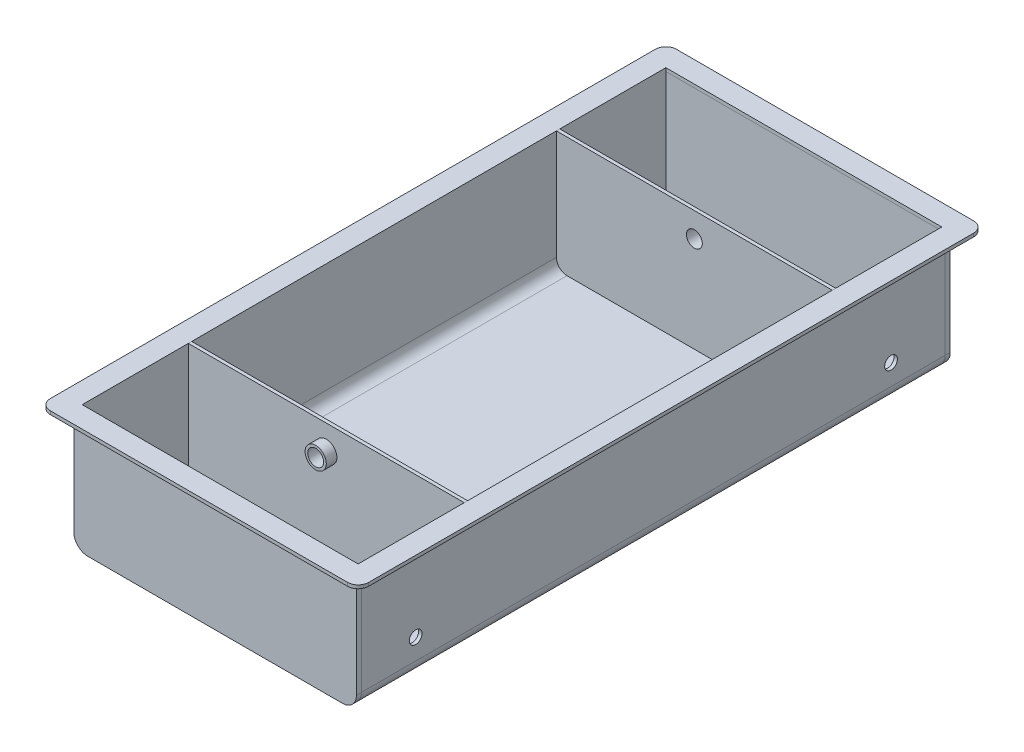
SolidWorks part; units mm, degrees
material "5052-H32"
ref_plane "Front Plane" through (0, 0, 0) normal (0, 0, 1) x (1, 0, 0)
ref_plane "Top Plane" through (0, 0, 0) normal (0, 1, 0) x (1, 0, 0)
ref_plane "Right Plane" through (0, 0, 0) normal (1, 0, 0) x (0, 0, -1)
sketch "Sketch2" plane through (0, 0, 0) normal (0, 0, 1) x (1, 0, 0)
  line L0 (-130, 0) -> (130, 0)
  line L1 (-130, 0) -> (-130, 110)
  line L2 (130, 0) -> (130, 110)
  line L3 (-133.175, -3.175) -> (-133.175, 110)
  line L4 (-133.175, -3.175) -> (133.175, -3.175)
  line L5 (133.175, -3.175) -> (133.175, 110)
  line L6 (-133.175, 110) -> (-130, 110)
  line L7 (130, 110) -> (133.175, 110)
  point P4 (0, 0)
  dimension "D1" = 260
  dimension "D3" = 110
  dimension "D4" = 110
  dimension "D2" = 3.175
  dimension "D5" = 3.175
  dimension "D6" = 3.175
extrude "Interior Dim" add sketch "Sketch2" against normal blind 550
fillet "Fillet2" radius 10 2 edges at (-130, 0, -275) (130, 0, -275)
fillet "Fillet3" radius 13.175 2 edges at (-133.175, -3.175, -275) (133.175, -3.175, -275)
ref_plane "Plane1" through (0, 0, 0) normal (0, 0, 1) x (1, 0, 0)
sketch "Sketch4" plane through (0, 0, 0) normal (0, 0, 1) x (1, 0, 0)
  line L0 (-130, 110) -> (130, 110)
  line L9 (-120, -3.175) -> (120, -3.175)
  line L10 (133.175, 10) -> (133.175, 110)
  line L11 (133.175, 110) -> (130, 110)
  line L12 (130, 110) -> (130, 10)
  line L13 (120, 0) -> (-120, 0)
  line L14 (-130, 10) -> (-130, 110)
  line L15 (-130, 110) -> (-133.175, 110)
  line L16 (-133.175, 110) -> (-133.175, 10)
  line L17 (-120, -3.175) -> (120, -3.175)
  line L18 (133.175, 10) -> (133.175, 110)
  line L19 (133.175, 110) -> (130, 110)
  line L23 (-130, 110) -> (-133.175, 110)
  line L24 (-133.175, 110) -> (-133.175, 10)
  arc A4 (120, -3.175) -> (133.175, 10) centre (120, 10) ccw
  arc A5 (120, 0) -> (130, 10) centre (120, 10) ccw
  arc A6 (-130, 10) -> (-120, 0) centre (-120, 10) ccw
  arc A7 (120, -3.175) -> (133.175, 10) centre (120, 10) ccw
  arc A9 (-133.175, 10) -> (-120, -3.175) centre (-120, 10) ccw
  arc A10 (-133.175, 10) -> (-120, -3.175) centre (-120, 10) ccw
  dimension "D1" = 0
extrude "Endcap1" add sketch "Sketch4" along normal blind 4.7625 separate body
ref_plane "Plane2" through (0, 0, -550) normal (0, 0, -1) x (-1, 0, 0)
sketch "Sketch5" plane through (0, 0, -550) normal (0, 0, -1) x (-1, 0, 0)
  line L8 (133.175, 110) -> (-133.175, 110)
  line L16 (-133.175, 110) -> (-133.175, 10)
  line L17 (-120, -3.175) -> (120, -3.175)
  line L18 (133.175, 10) -> (133.175, 110)
  line L19 (133.175, 110) -> (130, 110)
  line L20 (130, 110) -> (130, 10)
  line L21 (120, 0) -> (-120, 0)
  line L22 (-130, 10) -> (-130, 110)
  line L23 (-130, 110) -> (-133.175, 110)
  line L24 (-133.175, 110) -> (-133.175, 10)
  line L25 (-120, -3.175) -> (120, -3.175)
  line L26 (133.175, 10) -> (133.175, 110)
  arc A6 (-133.175, 10) -> (-120, -3.175) centre (-120, 10) ccw
  arc A7 (-133.175, 10) -> (-120, -3.175) centre (-120, 10) ccw
  arc A8 (120, 0) -> (130, 10) centre (120, 10) ccw
  arc A9 (-130, 10) -> (-120, 0) centre (-120, 10) ccw
  arc A12 (120, -3.175) -> (133.175, 10) centre (120, 10) ccw
  arc A13 (120, -3.175) -> (133.175, 10) centre (120, 10) ccw
  dimension "D1" = 0
ref_plane "Compartment1" through (0, 0, -100) normal (0, 0, -1) x (-1, 0, 0)
sketch "Sketch7" plane through (0, 0, -100) normal (0, 0, -1) x (-1, 0, 0)
  line L1 (130, 110) -> (-130, 110)
  line L10 (-120, -3.175) -> (120, -3.175)
  line L11 (-133.175, 110) -> (-133.175, 10)
  line L12 (-130, 110) -> (-133.175, 110)
  line L13 (-130, 10) -> (-130, 110)
  line L14 (120, 0) -> (-120, 0)
  line L15 (130, 110) -> (130, 10)
  line L16 (133.175, 110) -> (130, 110)
  line L17 (133.175, 10) -> (133.175, 110)
  line L21 (-130, 10) -> (-130, 110)
  line L22 (120, 0) -> (-120, 0)
  line L23 (130, 110) -> (130, 10)
  arc A5 (-130, 10) -> (-120, 0) centre (-120, 10) ccw
  arc A6 (120, 0) -> (130, 10) centre (120, 10) ccw
  arc A7 (-133.175, 10) -> (-120, -3.175) centre (-120, 10) ccw
  arc A8 (120, -3.175) -> (133.175, 10) centre (120, 10) ccw
  arc A9 (-130, 10) -> (-120, 0) centre (-120, 10) ccw
  arc A10 (120, 0) -> (130, 10) centre (120, 10) ccw
  dimension "D1" = 0
extrude "Compartment1_Boss" add sketch "Sketch7" along normal blind 3.175 separate body contours L22 A10 L23 L1 L21 A9 region at (0, 55.0793, -100)
ref_plane "Plane5" through (0, 110, 0) normal (0, 1, 0) x (1, 0, 0)
sketch "Sketch9" plane through (0, 110, 0) normal (0, 1, 0) x (1, 0, 0)
  line L0 (62.2463, 550) -> (-62.2463, 550) construction
  line L1 (-130, 550) -> (130, 550)
  line L2 (-130, 550) -> (-130, 0)
  line L3 (-130, 0) -> (130, 0)
  line L4 (130, 550) -> (130, 0)
  line L5 (-130, 0) -> (-130, 550) construction
  line L6 (-62.2463, 0) -> (62.2463, 0) construction
  line L7 (130, 550) -> (130, 0) construction
  line L8 (-150, 570) -> (-150, -20)
  line L9 (-150, -20) -> (150, -20)
  line L10 (150, 570) -> (150, -20)
  line L11 (-150, 570) -> (150, 570)
extrude "Lid_Flange" add sketch "Sketch9" along normal blind 3.175 separate body contours L11 L8 L9 L10 L1 L4 region at (0, 110, -563.3811)
fillet "Fillet4" radius 10 4 edges at (-150, 111.5875, -570) (150, 111.5875, -570) (150, 111.5875, 20) (-150, 111.5875, 20)
extrude "Endcap2" add sketch "Sketch5" along normal blind 4.7625 separate body
ref_plane "Compartment2" through (0, 0, -450) normal (0, 0, 1) x (1, 0, 0)
sketch "Sketch13" plane through (0, 0, -450) normal (0, 0, 1) x (1, 0, 0)
  line L0 (130, 110) -> (-130, 110)
  line L1 (133.175, 110) -> (130, 110) construction
  line L2 (130, 110) -> (130, 10) construction
  line L3 (-140, 110) -> (140, 110) construction
  line L4 (-130, 10) -> (-130, 110) construction
  line L5 (130, 110) -> (130, 10)
  line L6 (-130, 110) -> (-130, 10)
  line L7 (120, 0) -> (-120, 0)
  arc A0 (120, 0) -> (130, 10) centre (120, 10) ccw construction
  arc A1 (-130, 10) -> (-120, 0) centre (-120, 10) ccw construction
  arc A2 (-130, 10) -> (-120, 0) centre (-120, 10) ccw
  arc A3 (130, 10) -> (120, 0) centre (120, 10) cw
  dimension "D1" = 110
extrude "Compartment2_Boss" add sketch "Sketch13" along normal blind 3.175
sketch "Sketch16" plane through (-133.175, 0, 0) normal (-1, 0, 0) x (0, 0, 1)
  line L0 (-550, 0) -> (-450, 0) construction
  line L1 (-550, 110) -> (-550, 10) construction
  line L2 (0, 110) -> (0, 10) construction
  line L3 (-51, 29.5) -> (-499, 29.5) construction
  circle A0 centre (-499, 29.5) radius 6
  circle A1 centre (-51, 29.5) radius 6
  dimension "D1" = 12
  dimension "D4" = 12
  dimension "D2" = 29.5
  dimension "D3" = 51
  dimension "D5" = 51
extrude "Bearing_holes" cut sketch "Sketch16" against normal through all
sketch "Sketch17" plane through (0, 0, -450) normal (0, 0, -1) x (-1, 0, 0)
  line L0 (142.7388, 110) -> (-142.7388, 110) construction
  line L1 (130, 110) -> (130, 10) construction
  circle A0 centre (0, 90) radius 7.5
  circle A1 centre (0, 90) radius 10
  dimension "D1" = 15
  dimension "D4" = 20
  dimension "D2" = 20
  dimension "D3" = 130
extrude "Wire_Passthrough" cut sketch "Sketch17" against normal up to surface (350 mm away) contours A0 region at (0, 90, -450) up to face at (0, 39.3096, -100)
sketch "Sketch18" plane through (0, 110, 0) normal (0, 1, 0) x (1, 0, 0)
  line L1 (-130, 450) -> (130, 450)
  line L2 (-130, 450) -> (-130, 446.825)
  line L3 (-130, 446.825) -> (130, 446.825)
  line L4 (130, 450) -> (130, 446.825)
  line L5 (-130, 103.175) -> (130, 103.175)
  line L6 (-130, 103.175) -> (-130, 100)
  line L7 (-130, 100) -> (130, 100)
  line L8 (130, 103.175) -> (130, 100)
extrude "Boss-Extrude1" add sketch "Sketch18" along normal blind 3.18
extrude "Wire_Tube_2" add sketch "Sketch17<3>" along normal blind 10
sketch "Sketch17<3>" plane through (0, 0, -450) normal (0, 0, -1) x (-1, 0, 0) same geometry as "Sketch17"
sketch "Sketch19" plane through (0, 0, -100) normal (0, 0, 1) x (1, 0, 0)
  circle A0 centre (0, 90) radius 10
  circle M1 centre (0, 90) radius 7.5
  dimension "D1" = 20
extrude "Wire_Tube_1" add sketch "Sketch19" along normal blind 10 contours A0 M1 region at (-9.7172, 90, -100)
sketch "Sketch20" plane through (0, 110, 175) normal (0, 1, 0) x (1, 0, 0)
  line L0 (130, 450) -> (-130, 450) construction
  line L1 (-130, 725) -> (130, 725) construction
  line L2 (-130, 725) -> (-130, 175) construction
  line L3 (-130, 175) -> (130, 175) construction
  line L4 (130, 725) -> (130, 175) construction
  line L5 (130, 621.825) -> (130, 278.175) construction
  line L7 (0, 450) -> (0, 175) construction
  line L8 (-150, 745) -> (-150, 155) construction
  line L9 (-150, 155) -> (150, 155) construction
  line L10 (150, 745) -> (150, 155) construction
  line L11 (-150, 745) -> (150, 745) construction
  line L12 (-130, 621.825) -> (-130, 278.175) construction
  circle A0 centre (-140, 165) radius 2.5
  circle A2 centre (-140, 217) radius 2.5
  circle A3 centre (-140, 269) radius 2.5
  circle A4 centre (-140, 321) radius 2.5
  circle A5 centre (-140, 373) radius 2.5
  circle A6 centre (-140, 425) radius 2.5
  circle A7 centre (-140, 477) radius 2.5
  circle A8 centre (-140, 529) radius 2.5
  circle A9 centre (-140, 581) radius 2.5
  circle A10 centre (-140, 633) radius 2.5
  circle A16 centre (-140, 685) radius 2.5
  circle A17 centre (-84, 685) radius 2.5
  circle A18 centre (-28, 685) radius 2.5
  circle A19 centre (28, 685) radius 2.5
  circle A20 centre (84, 685) radius 2.5
  circle A21 centre (140, 685) radius 2.5
  circle A22 centre (140, 633) radius 2.5
  circle A23 centre (140, 581) radius 2.5
  circle A24 centre (140, 529) radius 2.5
  circle A25 centre (140, 477) radius 2.5
  circle A26 centre (140, 425) radius 2.5
  circle A27 centre (140, 373) radius 2.5
  circle A28 centre (140, 321) radius 2.5
  circle A29 centre (140, 269) radius 2.5
  circle A30 centre (140, 217) radius 2.5
  circle A31 centre (140, 165) radius 2.5
  circle A37 centre (84, 165) radius 2.5
  circle A38 centre (28, 165) radius 2.5
  circle A39 centre (-28, 165) radius 2.5
  circle A40 centre (-84, 165) radius 2.5
  point P8 (-130, 425)
  point P16 (-120, 425)
  point P69 (0, 0)
  dimension "D4" = 5
  dimension "D3" = 10
  dimension "D9" = 275
  dimension "D2" = 550
  dimension "D10" = 10
  dimension "D11" = 260
  dimension "D1" = 20
  dimension "D8" = 11
  dimension "D5" = 6
  dimension "D6" = 11
  dimension "D7" = 5
extrude "Bolt_Holes" [suppressed] cut sketch "Sketch20" along normal up to next
equation "\"L\"= 550"
equation "\"W\"= 260"
equation "\"D1@Sketch2\"=\"W\""
equation "\"D1@Interior Dim\" = \"L\""
equation "\"H\" = 110"
equation "\"D3@Sketch2\"=\"H\""
equation "\"D4@Sketch2\"=\"H\""
equation "\"Compartment Width\"= 100"
equation "\"D1@Compartment2\"=\"Compartment Width\""
equation "\"D1@Compartment1\"=\"Compartment Width\""
equation "\"D1@Sketch13\"=\"H\""
equation "\"D3@Sketch17\"=\"W\"/2"
equation "\"T\"= 4.7625 * 2 / 3"
equation "\"D1@Lid_Flange\"=\"T\""
equation "\"D1@Fillet3\"=\"T\"+10"
equation "\"D1@Compartment1_Boss\"=\"T\""
equation "\"D1@Compartment2_Boss\"=\"T\""
equation "\"D2@Sketch20\"=\"L\""
equation "\"D11@Sketch20\"=\"W\""
equation "\"D9@Sketch20\"=\"L\"/2"
